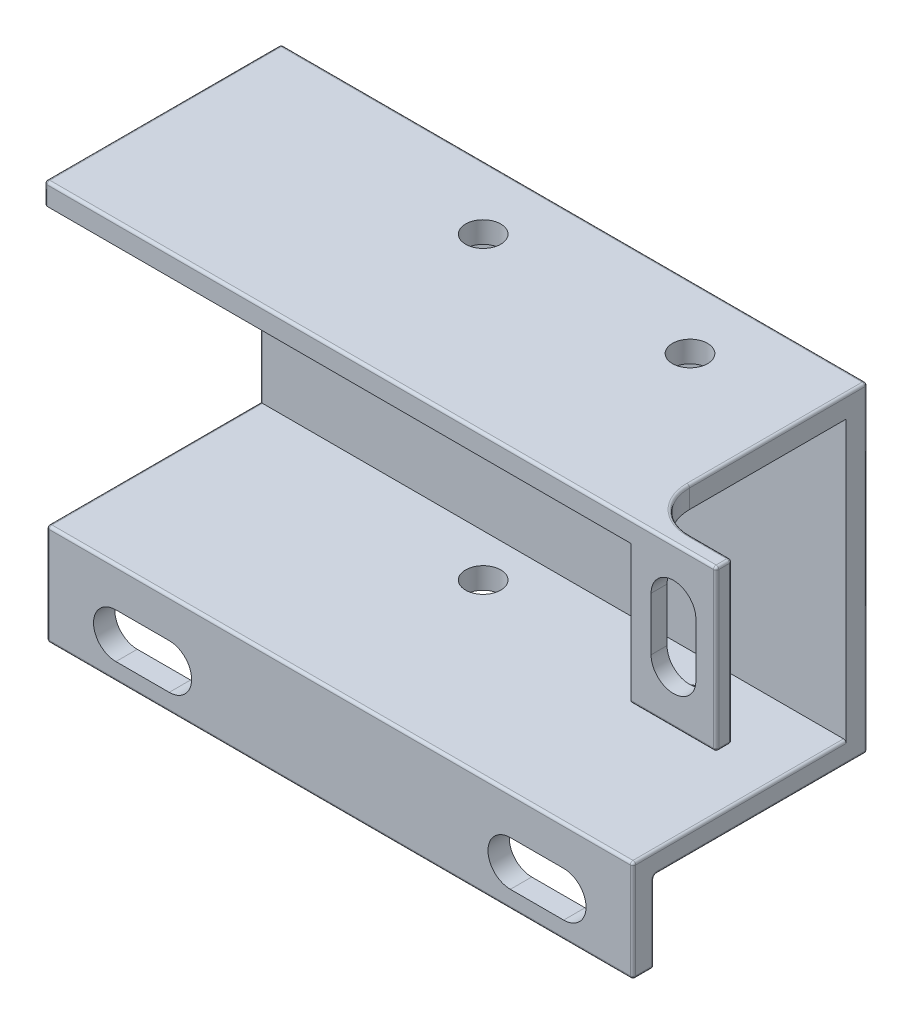
SolidWorks part; units mm, degrees
ref_plane "Front Plane" through (0, 0, 0) normal (0, 0, 1) x (1, 0, 0)
ref_plane "Top Plane" through (0, 0, 0) normal (0, 1, 0) x (1, 0, 0)
ref_plane "Right Plane" through (0, 0, 0) normal (1, 0, 0) x (0, 0, -1)
sketch "Sketch1" plane through (0, 0, 0) normal (1, 0, 0) x (0, 0, -1)
  line L0 (0, 0) -> (0, -9.5)
  line L1 (0, 0) -> (20, 0)
  line L2 (20, 0) -> (20, 26.1)
  line L3 (20, 26.1) -> (-0.2, 26.1)
  dimension "D1" = 26.1
  dimension "D2" = 20.2
  dimension "D3" = 9.5
  dimension "D4" = 20
extrude "Extrude-Thin2" add sketch "Sketch1" along normal mid plane 55 thin thin type one direction wall 2
sketch "Sketch2" plane through (0, 0, 0) normal (0, 1, 0) x (1, 0, 0)
  line L0 (-31.4759, 9.9) -> (35.6232, 9.9) construction
  line L1 (7.15, 27.9693) -> (7.15, -25.415) construction
  line L4 (27.5, 0) -> (27.5, 20) construction
  line L6 (27.5, 20) -> (-27.5, 20) construction
  circle A0 centre (-2.55, 3.8) radius 1.65
  circle A4 centre (-2.55, 16) radius 1.65
  circle A5 centre (16.85, 3.8) radius 1.65
  circle A6 centre (16.85, 16) radius 1.65
  dimension "D3" = 3.3
  dimension "D1" = 19.4
  dimension "D2" = 12.2
  dimension "D4" = 2.35
  dimension "D5" = 9
sketch "Sketch3" plane through (0, 0, 0) normal (0, 1, 0) x (1, 0, 0)
  circle A0 centre (-2.55, 3.8) radius 1.65 construction
  circle A1 centre (-2.55, 3.8) radius 1.65
extrude "Cut-Extrude1" [suppressed] cut sketch "Sketch3" against normal blind 10
sketch "Sketch4" plane through (0, 26.1, 0) normal (0, -1, 0) x (1, 0, 0)
  circle A0 centre (16.85, -16) radius 1.65 construction
  circle A1 centre (16.85, -16) radius 1.65
extrude "Cut-Extrude2" [suppressed] cut sketch "Sketch4" against normal blind 10
sketch "Sketch6" plane through (0, 0, 0) normal (0, 1, 0) x (1, 0, 0)
  circle A0 centre (-2.55, 16) radius 1.65 construction
  circle A1 centre (-2.55, 3.8) radius 1.65 construction
  circle A2 centre (16.85, 3.8) radius 1.65 construction
  circle A3 centre (16.85, 16) radius 1.65 construction
  circle A4 centre (-2.55, 16) radius 1.65
  circle A5 centre (-2.55, 3.8) radius 1.65 construction
  circle A6 centre (16.85, 3.8) radius 1.65 construction
  circle A7 centre (16.85, 16) radius 1.65
extrude "Cut-Extrude4" cut sketch "Sketch6" against normal through all both and the other way through all
fillet "Fillet1" [suppressed] radius 1
sketch "Sketch7" plane through (0, 0, 0) normal (1, 0, 0) x (0, 0, -1)
  line L0 (22, 0) -> (32, 0)
  line L1 (22, -2) -> (22, 28.1) construction
  dimension "D1" = 10
extrude "Extrude-Thin3" [suppressed] add sketch "Sketch7" along normal up to surface and the other way up to surface thin thin type one direction wall 2
sketch "Sketch8" plane through (0, 0, 0.2) normal (0, 0, 1) x (1, 0, 0)
  line L0 (27.5, 28.1) -> (27.5, 13.1)
  line L1 (27.5, 13.1) -> (35.5, 13.1)
  line L2 (35.5, 13.1) -> (35.5, 28.1)
  line L3 (35.5, 28.1) -> (27.5, 28.1)
  line L4 (27.5, 26.1) -> (27.5, 28.1) construction
  line L6 (-0.9, 28.1) -> (-4.2, 28.1) construction
  dimension "D1" = 15
  dimension "D2" = 8
  dimension "D3" = 0
extrude "Boss-Extrude1" add sketch "Sketch8" against normal blind 1.5
sketch "Sketch5" plane through (0, 0, 0) normal (0, 0, 1) x (1, 0, 0)
  line L0 (-39.5238, 13.05) -> (62.1219, 13.05) construction
  line L1 (0, 13.05) -> (0, 45.9107) construction
  line L12 (22.4726, 34.1) -> (17.4726, 34.1)
  line L13 (17.4726, 29.9) -> (22.4726, 29.9)
  line L15 (-17.4726, 29.9) -> (-22.4726, 29.9)
  line L16 (-22.4726, 34.1) -> (-17.4726, 34.1)
  arc A10 (22.4726, 34.1) -> (22.4726, 29.9) centre (22.1281, 32) cw
  arc A11 (17.4726, 34.1) -> (17.4726, 29.9) centre (17.1281, 32) ccw
  arc A12 (-17.4726, 34.1) -> (-17.4726, 29.9) centre (-17.1281, 32) cw
  arc A13 (-22.4726, 34.1) -> (-22.4726, 29.9) centre (-22.1281, 32) ccw
  dimension "D1" = 5
  dimension "D3" = 15
  dimension "D2" = 4.2
extrude "Cut-Extrude3" [suppressed] cut sketch "Sketch5" against normal blind 10 and the other way blind 10
sketch "Sketch9" plane through (0, 0, 0.2) normal (0, 0, -1) x (-1, 0, 0)
  line L0 (-29.4, 18) -> (-29.4, 23)
  line L1 (-33.6, 23) -> (-33.6, 18)
  line L2 (-31.5, 30.2356) -> (-31.5, 7.6247) construction
  line L3 (-27.5, 26.1) -> (-27.5, 13.1) construction
  line L4 (-35.5, 28.1) -> (-27.5, 28.1) construction
  line L5 (-35.5, 13.1) -> (-35.5, 28.1) construction
  arc A0 (-29.4, 18) -> (-33.6, 18) centre (-31.5, 18) cw
  arc A1 (-29.4, 23) -> (-33.6, 23) centre (-31.5, 23) ccw
  dimension "D3" = 3
  dimension "D1" = 5
  dimension "D2" = 4.2
extrude "Cut-Extrude5" cut sketch "Sketch9" along normal up to surface (1.5 mm away) up to face at (30.7, 21.7, -1.3)
sketch "Sketch10" [suppressed] plane through (0, 0, 0) normal (0, 1, 0) x (1, 0, 0)
  line L0 (14.421, 24.9) -> (19.421, 24.9)
  line L1 (19.421, 29.1) -> (14.421, 29.1)
  line L10 (0, -15.9667) -> (0, 39.3179) construction
  line L11 (-19.421, 29.1) -> (-14.421, 29.1)
  line L12 (-14.421, 24.9) -> (-19.421, 24.9)
  line L13 (31.0608, 27) -> (-33.0091, 27) construction
  line L14 (27.5, 32) -> (-27.5, 32) construction
  line L15 (27.5, 22) -> (-27.5, 22) construction
  arc A0 (14.421, 24.9) -> (14.421, 29.1) centre (14.421, 27) cw
  arc A1 (19.421, 24.9) -> (19.421, 29.1) centre (19.421, 27) ccw
  arc A10 (-19.421, 24.9) -> (-19.421, 29.1) centre (-19.421, 27) cw
  arc A11 (-14.421, 24.9) -> (-14.421, 29.1) centre (-14.421, 27) ccw
  dimension "D1" = 5
  dimension "D2" = 4.2
extrude "Cut-Extrude6" [suppressed] cut sketch "Sketch10" against normal blind 10
fillet "Fillet2" radius 4 1 edges at (27.5, 27.1, -1.3) tangent propagation no
fillet "Fillet3" radius 0.25 32 edges at (35.5, 20.6, -1.3) (35.5, 20.6, 0.2) (0, 28.1, -22) (-27.5, 13.05, -22) (27.5, 13.05, -22) (27.5, 0, -10) (31.5, 13.1, -1.3) (31.5, 13.1, 0.2) (35.5, 13.1, -0.55) (35.5, 28.1, -0.55) (4, 28.1, 0.2) (27.5, -9.5, -1) (-27.5, -9.5, -1) (-27.5, 27.1, 0.2) (-27.5, 0, -10) (-27.5, -4.75, 0) (0, 0, 0) (27.5, -4.75, 0) (0, -9.5, 0) (0, -9.5, -2) (-27.5, -5.75, -2) (27.5, -5.75, -2) (0, -2, -2) (27.5, -2, -12) (0, -2, -22) (-27.5, -2, -12) (27.5, 28.1, -13.65) (28.6716, 28.1, -2.4716) (33.5, 28.1, -1.3) (-27.5, 28.1, -10.9) (-27.5, 26.1, -9.9) (-27.5, 13.05, -20) tangent propagation no
fillet "Fillet4" [suppressed] radius 1
sketch "Sketch11" plane through (0, 0, -2) normal (0, 0, -1) x (-1, 0, 0)
  line L0 (-21, -7.85) -> (-16, -7.85)
  line L1 (-16, -3.65) -> (-21, -3.65)
  line L2 (31.6058, -5.75) -> (-40.007, -5.75) construction
  line L3 (-27.25, -9.5) -> (27.25, -9.5) construction
  line L4 (-27.5, -2) -> (27.5, -2) construction
  line L5 (0, 20.515) -> (0, -17.4276) construction
  line L6 (16, -3.65) -> (21, -3.65)
  line L7 (21, -7.85) -> (16, -7.85)
  arc A0 (-21, -7.85) -> (-21, -3.65) centre (-21, -5.75) cw
  arc A1 (-16, -7.85) -> (-16, -3.65) centre (-16, -5.75) ccw
  arc A2 (16, -7.85) -> (16, -3.65) centre (16, -5.75) cw
  arc A3 (21, -7.85) -> (21, -3.65) centre (21, -5.75) ccw
  point P21 (0, 0)
  point P22 (0, 0)
  dimension "D1" = 4.2
  dimension "D2" = 16
  dimension "D3" = 5
extrude "Cut-Extrude7" cut sketch "Sketch11" against normal blind 10
fillet "Fillet5" radius 1 1 edges at (29.5, 26.1, -1.3)
